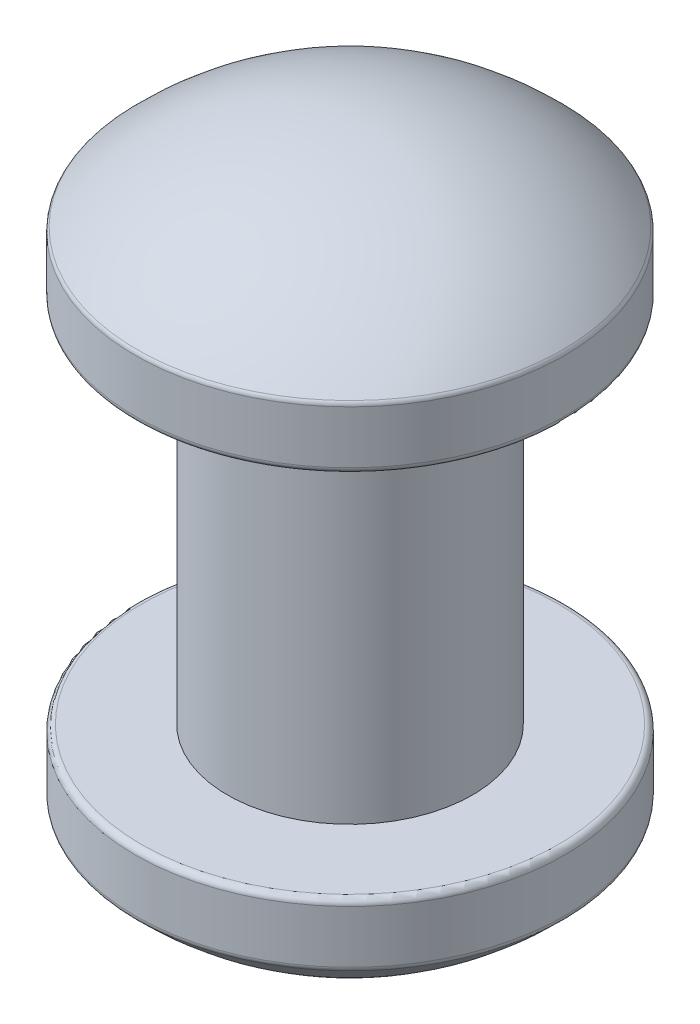
SolidWorks part; units mm, degrees
ref_plane "前视基准面" through (0, 0, 0) normal (0, 0, 1) x (1, 0, 0)
ref_plane "上视基准面" through (0, 0, 0) normal (0, 1, 0) x (1, 0, 0)
ref_plane "右视基准面" through (0, 0, 0) normal (1, 0, 0) x (0, 0, -1)
sketch "Sketch1" plane through (0, 0, 0) normal (0, 0, 1) x (1, 0, 0)
  line L0 (0, -0.4) -> (0, 0.4)
  line L1 (0, 0.4) -> (0.35, 0.4)
  line L2 (0.35, 0.4) -> (0.35, 0.3)
  line L3 (0.35, 0.3) -> (0.2, 0.3)
  line L4 (0.2, 0.3) -> (0.2, -0.3)
  line L5 (0.2, 0) -> (0, 0) construction
  line L6 (0.35, -0.3) -> (0.2, -0.3)
  line L7 (0.35, -0.4) -> (0.35, -0.3)
  line L8 (0, -0.4) -> (0.35, -0.4)
  point P3 (0.35, 0.35)
  point P8 (0, 0)
  point P9 (0, 0)
  dimension "D1" = 0.2
  dimension "D2" = 0.3
  dimension "D3" = 0.05
  dimension "D4" = 0.15
revolve "Revolve1" add sketch "Sketch1" angle 360 about L0
dome "Dome1" faces to dome 1 distance 0.15 reverse direction no elliptical dome no face at (0, 0.4, -0.35) parameters "D1"=0.15
dome "Dome2" faces to dome 1 distance 0.15 reverse direction no elliptical dome no face at (0, -0.4, -0.35) parameters "D1"=0.15
fillet "Fillet1" radius 0.01 4 edges at (0, -0.4, -0.35) (0, -0.3, -0.35) (0, 0.3, -0.35) (0, 0.4, -0.35)
